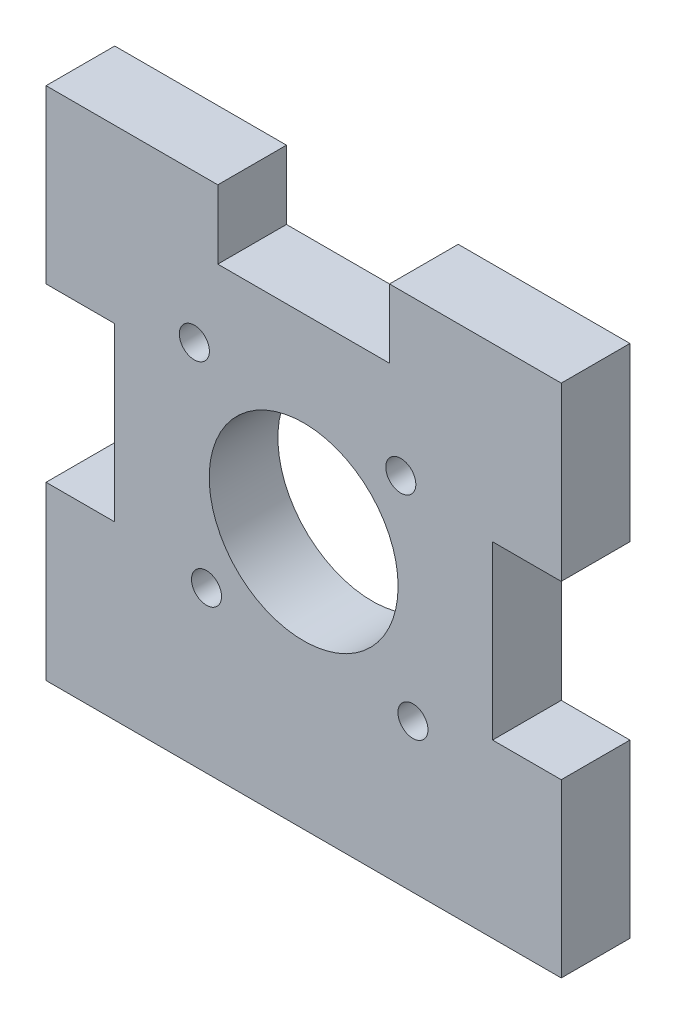
SolidWorks part; units mm, degrees
ref_plane "Front" through (0, 0, 0) normal (0, 0, 1) x (1, 0, 0)
ref_plane "Top" through (0, 0, 0) normal (0, 1, 0) x (1, 0, 0)
ref_plane "Right" through (0, 0, 0) normal (1, 0, 0) x (0, 0, -1)
sketch "Skizze1" plane through (0, 0, 0) normal (0, 0, 1) x (1, 0, 0)
  line L1 (15, 15) -> (-15, 15)
  line L2 (15, 15) -> (15, -15)
  line L3 (15, -15) -> (-15, -15)
  line L4 (-15, 15) -> (-15, -15)
  line L5 (15, 15) -> (-15, -15) construction
  line L6 (15, -15) -> (-15, 15) construction
  point P0 (0, 0)
  dimension "D1" = 30
  dimension "D2" = 30
extrude "Aufsatz-Linear austragen1" add sketch "Skizze1" along normal blind 4
sketch "Skizze2" plane through (0, 0, 4) normal (0, 0, 1) x (1, 0, 0)
  line L0 (0, 0) -> (0, 10.7157) construction
  line L1 (-5.6569, -5.6569) -> (5.6569, 5.6569) construction
  line L2 (-6.364, 6.364) -> (6.364, -6.364) construction
  circle A0 centre (0, 0) radius 5.5
  circle A1 centre (5.6569, 5.6569) radius 0.875
  circle A2 centre (6.364, -6.364) radius 0.875
  circle A3 centre (-5.6569, -5.6569) radius 0.875
  circle A4 centre (-6.364, 6.364) radius 0.875
  dimension "D1" = 11
  dimension "D3" = 1.75
  dimension "D2" = 45
  dimension "D4" = 16
  dimension "D5" = 18
extrude "Schnitt-Linear austragen1" cut sketch "Skizze2" against normal blind 4
sketch "Skizze3" plane through (0, 0, 4) normal (0, 0, 1) x (1, 0, 0)
  line L0 (0, 15) -> (0, 0) construction
  line L1 (15, 15) -> (-15, 15) construction
  line L2 (0, 0) -> (-15, 0) construction
  line L3 (-15, 15) -> (-15, -15) construction
  line L4 (-15, -5) -> (-15, 5)
  line L5 (-15, 5) -> (-11, 5)
  line L6 (-11, 5) -> (-11, -5)
  line L7 (-15, -5) -> (-11, -5)
  line L8 (-5, 15) -> (-5, 11)
  line L9 (-5, 15) -> (5, 15)
  line L10 (5, 15) -> (5, 11)
  line L11 (5, 11) -> (-5, 11)
  line L12 (15, 5) -> (11, 5)
  line L13 (15, 5) -> (15, -5)
  line L14 (15, -5) -> (11, -5)
  line L15 (11, -5) -> (11, 5)
  line L16 (0, 0) -> (-11, 5) construction
  line L17 (0, 0) -> (5, 11) construction
  point P12 (-11, 0)
  point P13 (0, 0)
  dimension "D1" = 4
  dimension "D2" = 10
  dimension "D4" = 90
  dimension "D3" = 3
extrude "Schnitt-Linear austragen2" cut sketch "Skizze3" against normal through all
